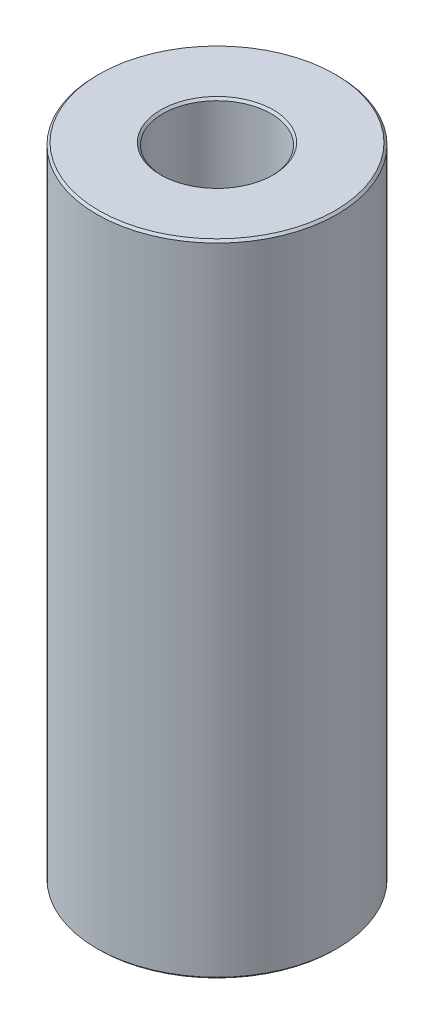
SolidWorks part; units mm, degrees
ref_plane "Front Plane" through (0, 0, 0) normal (0, 0, 1) x (1, 0, 0)
ref_plane "Top Plane" through (0, 0, 0) normal (0, 1, 0) x (1, 0, 0)
ref_plane "Right Plane" through (0, 0, 0) normal (1, 0, 0) x (0, 0, -1)
sketch "Sketch1" plane through (0, 0, 0) normal (0, 1, 0) x (1, 0, 0)
  circle A0 centre (0, 0) radius 47.5
  dimension "SLEEVE_OD" = 95
extrude "Boss-Extrude1" add sketch "Sketch1" along normal blind 252.8397
sketch "Sketch2" plane through (0, 0, 0) normal (0, 1, 0) x (1, 0, 0)
  circle A0 centre (0, 0) radius 21.3995
  dimension "BORE_D" = 42.799
extrude "Cut-Extrude1" cut sketch "Sketch2" along normal through all
chamfer "Chamfer1" distance 0.857 angle 45 4 edges at (0, 252.8397, 21.3995) (0, 0, 21.3995) (0, 0, 47.5) (0, 252.8397, 47.5)
